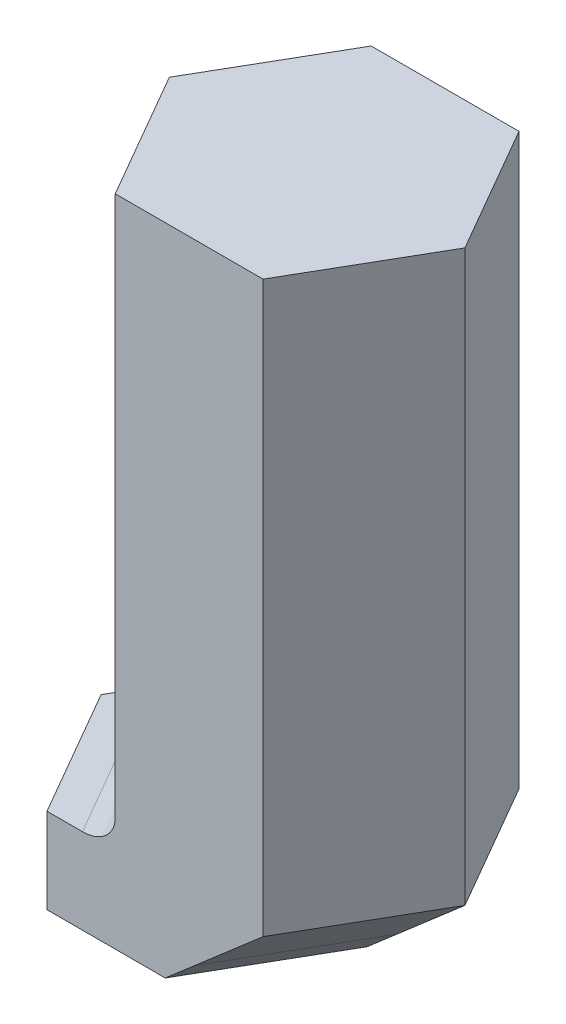
SolidWorks part; units mm, degrees
ref_plane "前视基准面" through (0, 0, 0) normal (0, 0, 1) x (1, 0, 0)
ref_plane "上视基准面" through (0, 0, 0) normal (0, 1, 0) x (1, 0, 0)
ref_plane "右视基准面" through (0, 0, 0) normal (1, 0, 0) x (0, 0, -1)
other "Configuration Table"
sketch "草图1" plane through (0, 0, 0) normal (0, 1, 0) x (1, 0, 0)
  line L1 (2.5981, -4.5) -> (5.1962, 0)
  line L2 (5.1962, 0) -> (2.5981, 4.5)
  line L3 (2.5981, 4.5) -> (-2.5981, 4.5)
  line L4 (-2.5981, 4.5) -> (-5.1962, 0)
  line L5 (-5.1962, 0) -> (-2.5981, -4.5)
  line L6 (-2.5981, -4.5) -> (2.5981, -4.5)
  circle A0 centre (0, 0) radius 4.5 construction
  dimension "D1" = 9
extrude "凸台-拉伸1" add sketch "草图1" along normal blind 20
sketch "草图2" plane through (0, 0, 0) normal (0, -1, 0) x (-1, 0, 0)
  line L0 (-2.5981, 4.5) -> (2.5981, 4.5) construction
  line L1 (7.5962, 0) -> (4.9981, 4.5)
  line L2 (4.9981, 4.5) -> (-0.1981, 4.5)
  line L3 (-0.1981, 4.5) -> (-2.7962, 0)
  line L4 (-2.7962, 0) -> (-0.1981, -4.5)
  line L5 (-0.1981, -4.5) -> (4.9981, -4.5)
  line L6 (4.9981, -4.5) -> (7.5962, 0)
  circle A0 centre (2.4, 0) radius 4.5 construction
  dimension "D1" = 9
  dimension "D2" = 0
  dimension "D3" = 2.4
extrude "凸台-拉伸2" add sketch "草图2" along normal blind 3
chamfer "倒角1" distance 2.1 angle 45 2 edges at (1.4971, 0, -2.25) (1.4971, 0, 2.25)
chamfer "倒角2" distance 0.9 angle 45 2 edges at (1.4971, -3, 2.25) (1.4971, -3, -2.25)
fillet "圆角2" radius 1 2 edges at (-3.8971, 0, -2.25) (-3.8971, 0, 2.25)
